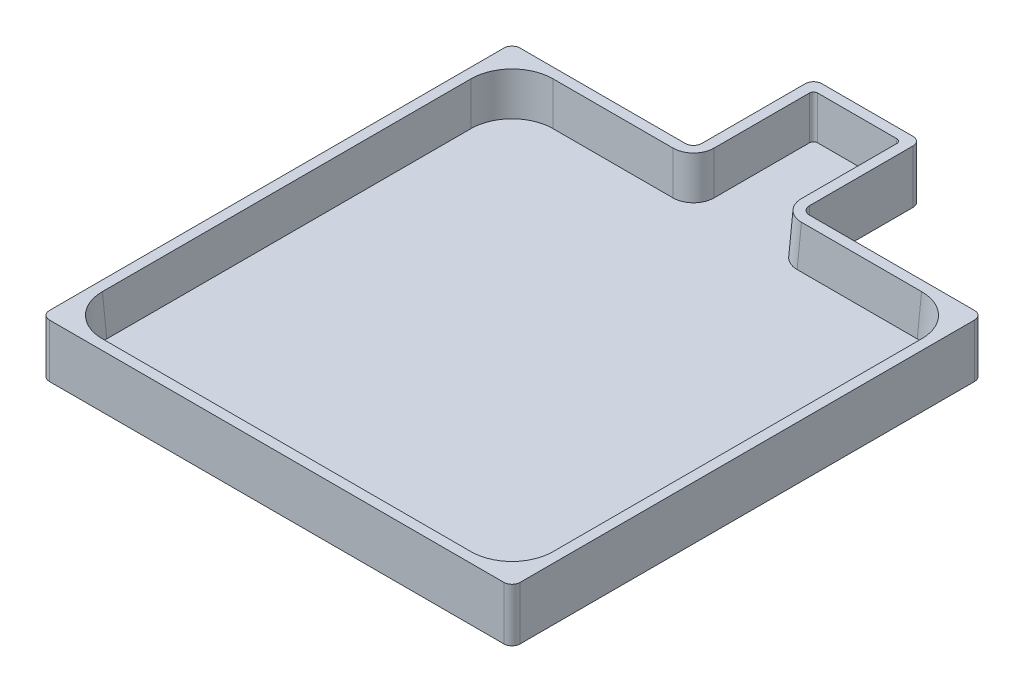
SolidWorks part; units mm, degrees
note: The reader was unsure of these and kept them because the rebuilt part matched: shared geometry of "Sketch2<5>".
ref_plane "Front Plane" through (0, 0, 0) normal (0, 0, 1) x (1, 0, 0)
ref_plane "Top Plane" through (0, 0, 0) normal (0, 1, 0) x (1, 0, 0)
ref_plane "Right Plane" through (0, 0, 0) normal (1, 0, 0) x (0, 0, -1)
sketch "Sketch2" plane through (0, 0, 0) normal (0, 1, 0) x (1, 0, 0)
  line L0 (54.4, -44.4) -> (54.4, 44.4)
  line L1 (44.4, 54.4) -> (13.1371, 54.4)
  line L2 (-54.4, 44.4) -> (-54.4, -44.4)
  line L3 (-44.4, -54.4) -> (44.4, -54.4)
  line L4 (-57.4, 44.4) -> (-57.4, -44.4)
  line L5 (-44.4, -57.4) -> (44.4, -57.4)
  line L6 (57.4, -44.4) -> (57.4, 44.4)
  line L7 (44.4, 57.4) -> (13.1371, 57.4)
  line L8 (44.4, -44.4) -> (-44.4, 44.4) construction
  line L10 (13.1371, 86.6628) -> (-13.1371, 86.6628)
  line L11 (13.1371, 86.6628) -> (13.1371, 57.4)
  line L13 (-13.1371, 86.6628) -> (-13.1371, 57.4)
  line L14 (-13.1371, 54.4) -> (-44.4, 54.4)
  line L15 (44.4, 54.4) -> (-44.4, 54.4) construction
  line L16 (-13.1371, 57.4) -> (-44.4, 57.4)
  line L17 (44.4, 57.4) -> (-44.4, 57.4) construction
  line L18 (10.1371, 83.6628) -> (10.1371, 57.4)
  line L19 (10.1371, 83.6628) -> (-10.1371, 83.6628)
  line L20 (-10.1371, 83.6628) -> (-10.1371, 57.4)
  line L22 (-10.1371, 83.6628) -> (-10.1371, 54.4) construction
  line L23 (10.1371, 83.6628) -> (10.1371, 54.4) construction
  line L25 (-13.1371, 86.6628) -> (-13.1371, 54.4) construction
  line L26 (13.1371, 86.6628) -> (13.1371, 54.4) construction
  line L27 (0, 0) -> (0, 83.6628) construction
  line L29 (-57.4, 44.4) -> (-57.4, 57.4)
  line L30 (-57.4, 57.4) -> (-44.4, 57.4)
  line L33 (-54.4, 44.4) -> (-54.4, 54.4)
  line L34 (-54.4, 54.4) -> (-44.4, 54.4)
  line L36 (57.4, 44.4) -> (57.4, 57.4)
  line L37 (57.4, 57.4) -> (44.4, 57.4)
  line L38 (54.4, 54.4) -> (44.4, 54.4)
  line L39 (54.4, 44.4) -> (54.4, 54.4)
  line L40 (0, 0) -> (57.4, 0) construction
  line L41 (54.4, -44.4) -> (54.4, -54.4)
  line L42 (57.4, -44.4) -> (57.4, -57.4)
  line L43 (54.4, -54.4) -> (44.4, -54.4)
  line L44 (57.4, -57.4) -> (44.4, -57.4)
  line L45 (-54.4, -54.4) -> (-44.4, -54.4)
  line L46 (-57.4, -57.4) -> (-44.4, -57.4)
  line L47 (-57.4, -44.4) -> (-57.4, -57.4)
  line L48 (-54.4, -44.4) -> (-54.4, -54.4)
  line L49 (10.1371, 57.4) -> (10.1371, 54.4)
  line L50 (-13.1371, 54.4) -> (-10.1371, 54.4)
  line L53 (-10.1371, 54.4) -> (-10.1371, 57.4)
  line L54 (10.1371, 54.4) -> (13.1371, 54.4)
  arc A3 (44.4, -54.4) -> (54.4, -44.4) centre (44.4, -44.4) ccw construction
  arc A4 (-57.4, -44.4) -> (-44.4, -57.4) centre (-44.4, -44.4) ccw construction
  arc A5 (44.4, -57.4) -> (57.4, -44.4) centre (44.4, -44.4) ccw construction
  arc A10 (-44.4, 54.4) -> (-54.4, 44.4) centre (-44.4, 44.4) ccw construction
  arc A11 (-44.4, 57.4) -> (-57.4, 44.4) centre (-44.4, 44.4) ccw construction
  arc A12 (54.4, 44.4) -> (44.4, 54.4) centre (44.4, 44.4) ccw construction
  arc A13 (57.4, 44.4) -> (44.4, 57.4) centre (44.4, 44.4) ccw construction
  arc A14 (-54.4, -44.4) -> (-44.4, -54.4) centre (-44.4, -44.4) ccw construction
  point P24 (0, 0)
  point P25 (0, 0)
  dimension "D4" = 13
  dimension "D2" = 114.8
  dimension "D3" = 88.8
  dimension "D5" = 88.8
  dimension "D6" = 108.8
  dimension "D15" = 29.2628
  dimension "D1" = 3
  dimension "D16" = 3
extrude "Boss-Extrude3" add sketch "Sketch2" along normal blind 3
extrude "Boss-Extrude4" add sketch "Sketch2<5>" along normal blind 10 from surface at 3 starting at face at (0, 3, -36.0157)
sketch "Sketch2<5>" plane through (0, 0, 0) normal (0, 1, 0) x (1, 0, 0) same geometry as "Sketch2"
draft "Draft12" type of draft neutral plane draft angle 3 faces to draft 8 face at (-10.1371, 8, -69.0314) face at (-32.2685, 8, -54.4) face at (-54.4, 8, 0) face at (0, 8, 54.4) face at (54.4, 8, 0) face at (0, 8, -83.6628) face at (32.2685, 8, -54.4) face at (10.1371, 8, -69.0314) neutral plane through (0, 3, 0) neutral plane normal (0, 1, 0) parameters "D1"=3
fillet "Fillet1" radius 2 8 edges at (13.1371, 6.5, -57.4) (-13.1371, 6.5, -86.6628) (-13.1371, 6.5, -57.4) (-57.4, 6.5, -57.4) (13.1371, 6.5, -86.6628) (57.4, 6.5, -57.4) (57.4, 6.5, 57.4) (-57.4, 6.5, 57.4)
fillet "Fillet3" radius 10 4 edges at (-54.662, 8, -54.662) (-54.662, 8, 54.662) (54.662, 8, 54.662) (54.662, 8, -54.662)
fillet "Fillet4" radius 5 2 edges at (10.3991, 8, -54.662) (-10.3991, 8, -54.662)
fillet "Fillet5" radius 1 2 edges at (-10.3991, 8, -83.9248) (10.3991, 8, -83.9248)
